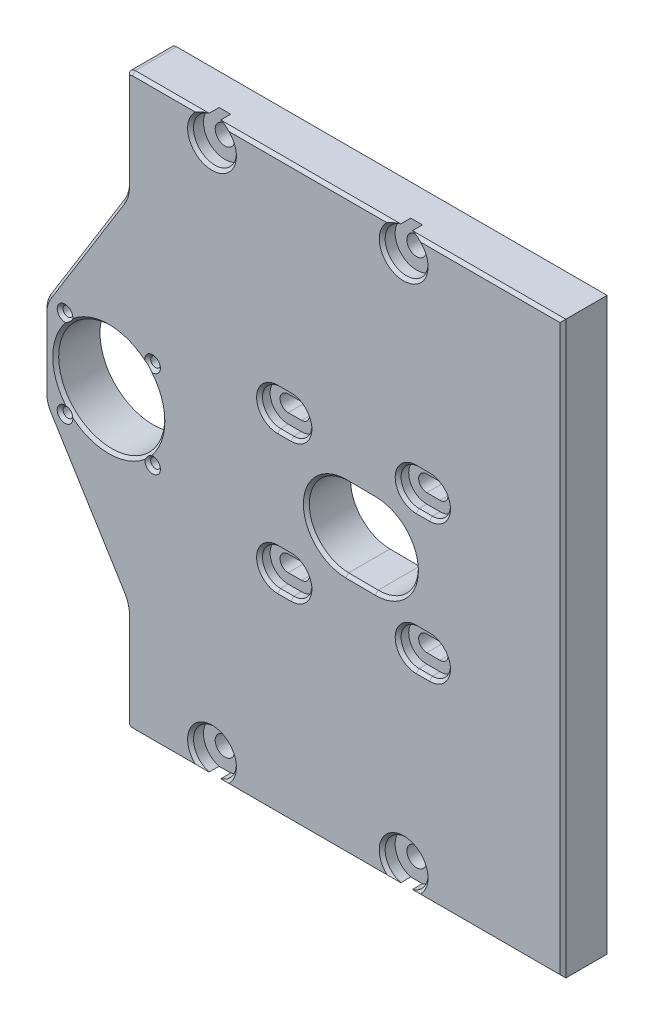
SolidWorks part; units mm, degrees
ref_plane "Front Plane" through (0, 0, 0) normal (0, 0, 1) x (1, 0, 0)
ref_plane "Top Plane" through (0, 0, 0) normal (0, 1, 0) x (1, 0, 0)
ref_plane "Right Plane" through (0, 0, 0) normal (1, 0, 0) x (0, 0, -1)
sketch "Sketch1" plane through (0, 0, 0) normal (0, 0, 1) x (1, 0, 0)
  line L6 (-12, 227) -> (0, 227)
  line L24 (-148, 255) -> (-148, 190) construction
  line L31 (-148, 70) -> (-148, 10) construction
  line L32 (-148, 33.5) -> (-12, 33.5) construction
  line L34 (0, 227) -> (0, 33.5)
  line L36 (-12, 227) -> (-148, 227) construction
  line L37 (-148, 227) -> (-148, 190)
  line L38 (-148, 70) -> (-148, 33.5)
  line L39 (-148, 33.5) -> (-12, 33.5)
  line L43 (-12, 227) -> (-148, 227)
  line L45 (-176, 115.2267) -> (-176, 144.7733)
  line L46 (-176, 144.7733) -> (-148, 190)
  line L47 (-176, 115.2267) -> (-148, 70)
  line L52 (0, 33.5) -> (-12, 33.5)
  circle A8 centre (-154, 130) radius 18
  circle A10 centre (-154, 130) radius 18
  dimension "D1" = 1
extrude "Boss-Extrude1" add sketch "Sketch1" along normal blind 15
sketch "Sketch2" plane through (0, 0, 15) normal (0, 0, 1) x (1, 0, 0)
  circle A1 centre (-139.1508, 115.1508) radius 2.25
  circle A3 centre (-168.8492, 115.1508) radius 2.25
  circle A5 centre (-168.8492, 144.8492) radius 2.25
  circle A7 centre (-139.1508, 144.8492) radius 2.25
hole_wizard "M4x0.7 Tapped Hole1" positions "Sketch3" profile "Sketch4" tap size "M4x0.7" standard "ANSI Metric"
sketch "Sketch3" plane through (0, 0, 15) normal (0, 0, 1) x (1, 0, 0)
  point P0 (-168.8492, 144.8492)
  point P3 (-139.1508, 144.8492)
  point P6 (-139.1508, 115.1508)
  point P9 (-168.8492, 115.1508)
sketch "Sketch4" plane through (-168.8492, 144.8492, 15) normal (1, 0, 0) x (0, -1, 0)
  line L0 (0, 0) -> (0, 20)
  line L1 (0, 20) -> (1.65, 19.0086)
  line L2 (1.65, 19.0086) -> (1.65, 0)
  line L5 (1.65, 0) -> (0, 0)
  line L10 (0, 20) -> (-1.65, 19.0086) construction
  line L11 (0, -6.35) -> (0, 107.95) construction
  dimension "Tap Drill Dia." = 3.3
  dimension "Tap Drill Depth" = 20
  dimension "Drill Angle" = 118
cosmetic thread "Hole Thread1" parameters "D1"=12, "D2"=4
cosmetic thread "Hole Thread2" parameters "D1"=12, "D2"=4
cosmetic thread "Hole Thread3" parameters "D1"=12, "D2"=4
cosmetic thread "Hole Thread4" parameters "D1"=12, "D2"=4
hole_wizard "CBORE for M6 Hex Head Bolt1" positions "Sketch5" profile "Sketch6" counterbore size "M6" standard "ANSI Metric"
sketch "Sketch5" plane through (0, 0, 15) normal (0, 0, 1) x (1, 0, 0)
  point P0 (-54, 220)
  point P3 (-119, 220)
  point P6 (-54, 40.5)
  point P9 (-119, 40.5)
sketch "Sketch6" plane through (-54, 220, 15) normal (1, 0, 0) x (0, -1, 0)
  line L0 (0, 0) -> (0, 29.9828)
  line L1 (0, 29.9828) -> (3.3, 28)
  line L2 (3.3, 28) -> (3.3, 4.38)
  line L3 (3.3, 4.38) -> (7.275, 4.38)
  line L4 (7.275, 4.38) -> (7.275, 0)
  line L5 (7.275, 0) -> (0, 0)
  line L10 (0, 29.9828) -> (-3.3, 28) construction
  line L11 (0, -6.35) -> (0, 107.95) construction
  dimension "Hole Dia." = 6.6
  dimension "Hole Depth" = 28
  dimension "C'Bore Dia." = 14.55
  dimension "C'Bore Depth" = 4.38
  dimension "Drill Angle" = 118
sketch "Sketch7" plane through (0, 0, 15) normal (0, 0, 1) x (1, 0, 0)
  line L0 (-73.5, 129.1439) -> (-88.5, 129.1439)
  line L1 (-89.5, 152.6439) -> (-94.5, 152.6439)
  line L2 (-42.5, 152.6439) -> (-47.5, 152.6439)
  line L3 (-42.5, 105.6439) -> (-47.5, 105.6439)
  line L4 (-89.5, 105.6439) -> (-94.5, 105.6439)
  circle A1 centre (-50, 105.6439) radius 2.85 construction
  circle A2 centre (-73.5, 129.1439) radius 13.5
  circle A3 centre (-73.5, 129.1439) radius 13.5
  circle A4 centre (-97, 105.6439) radius 2.85 construction
  circle A5 centre (-97, 152.6439) radius 2.85 construction
  circle A6 centre (-50, 152.6439) radius 2.85 construction
  circle A7 centre (-50, 105.6439) radius 2.85
  circle A8 centre (-97, 105.6439) radius 2.85
  circle A9 centre (-97, 152.6439) radius 2.85
  circle A10 centre (-50, 152.6439) radius 2.85
  dimension "D1" = 1
hole_wizard "Ø1.0mm Dowel Slot1" positions "Sketch8" profile "Sketch9" size "Ø1.0" standard "ANSI Metric" slot yes
sketch "Sketch8" plane through (0, 0, 15) normal (0, 0, 1) x (1, 0, 0)
  line L0 (-86.9991, 129.3233) -> (-50.0009, 128.9645) construction
  point P0 (-68.5, 129.1439)
  dimension "D1" = 37
sketch "Sketch9" plane through (-68.5, 129.1439, 15) normal (1, 0, 0) x (0, -1, 0)
  line L0 (0, 0) -> (0, 36.1116)
  line L1 (0, 36.1116) -> (13.5, 28)
  line L2 (13.5, 28) -> (13.5, 0)
  line L5 (13.5, 0) -> (0, 0)
  line L10 (0, 36.1116) -> (-13.5, 28) construction
  line L11 (0, -6.35) -> (0, 107.95) construction
  dimension "Hole Dia." = 27
  dimension "Hole Depth" = 28
  dimension "Drill Angle" = 118
hole_wizard "CBORE SLOT for M5 Hex Head Bolt1" positions "Sketch10" profile "Sketch11" size "M5" standard "ANSI Metric" slot yes
sketch "Sketch10" plane through (0, 0, 15) normal (0, 0, 1) x (1, 0, 0)
  line L0 (-99.5, 152.6439) -> (-89.5, 152.6439) construction
  point P0 (-94.5, 152.6439)
  point P5 (-94.5, 105.6439)
  point P8 (-47.5, 152.6439)
  point P11 (-47.5, 105.6439)
  dimension "D1" = 10
sketch "Sketch11" plane through (-94.5, 152.6439, 15) normal (1, 0, 0) x (0, -1, 0)
  line L0 (0, 0) -> (0, 29.6524)
  line L1 (0, 29.6524) -> (2.75, 28)
  line L2 (2.75, 28) -> (2.75, 3.58)
  line L3 (2.75, 3.58) -> (6.12, 3.58)
  line L4 (6.12, 3.58) -> (6.12, 0)
  line L5 (6.12, 0) -> (0, 0)
  line L10 (0, 29.6524) -> (-2.75, 28) construction
  line L11 (0, -6.35) -> (0, 107.95) construction
  dimension "Hole Dia." = 5.5
  dimension "Hole Depth" = 28
  dimension "C'Bore Dia." = 12.24
  dimension "C'Bore Depth" = 3.58
  dimension "Drill Angle" = 118
fillet "Fillet1" radius 10 4 edges at (-148, 70, 7.5) (-176, 115.2267, 7.5) (-176, 144.7733, 7.5) (-148, 190, 7.5)
fillet "Fillet2" radius 2 2 edges at (-148, 33.5, 7.5) (-148, 227, 7.5)
chamfer "Chamfer1" distance 1 angle 45 47 edges at (-148.3817, 69.8914, 15) (-162, 92.6134, 15) (-175.6183, 115.3353, 15) (-176, 130, 15) (-175.6183, 144.6647, 15) (-162, 167.3866, 15) (-148.3817, 190.1086, 15) (-148, 208.9225, 15) (-147.4142, 226.4142, 15) (-133.4907, 227, 15) (-119, 212.725, 15) (-86.5, 227, 15) (-54, 212.725, 15) (-26.0093, 227, 15) (-26.0093, 33.5, 15) (-54, 47.775, 15) (-86.5, 33.5, 15) (-119, 47.775, 15) (-133.4907, 33.5, 15) (-147.4142, 34.0858, 15) (-148, 51.3275, 15) (-167.1992, 115.1508, 15) (-137.5008, 115.1508, 15) (-137.5008, 144.8492, 15) (-167.1992, 144.8492, 15) (-86.9991, 129.3233, 15) (-68.6309, 115.6445, 15) (-50.0009, 128.9645, 15) (-68.3691, 142.6433, 15) (-55.87, 105.6439, 15) (-47.5, 99.5239, 15) (-39.13, 105.6439, 15) (-47.5, 111.7639, 15) (-47.5, 146.5239, 15) (-39.13, 152.6439, 15) (-47.5, 158.7639, 15) (-55.87, 152.6439, 15) (-94.5, 99.5239, 15) (-86.13, 105.6439, 15) (-94.5, 111.7639, 15) (-102.87, 105.6439, 15) (-102.87, 152.6439, 15) (-94.5, 146.5239, 15) (-86.13, 152.6439, 15) (-94.5, 158.7639, 15) (-136, 130, 15) (0, 130.25, 15)
